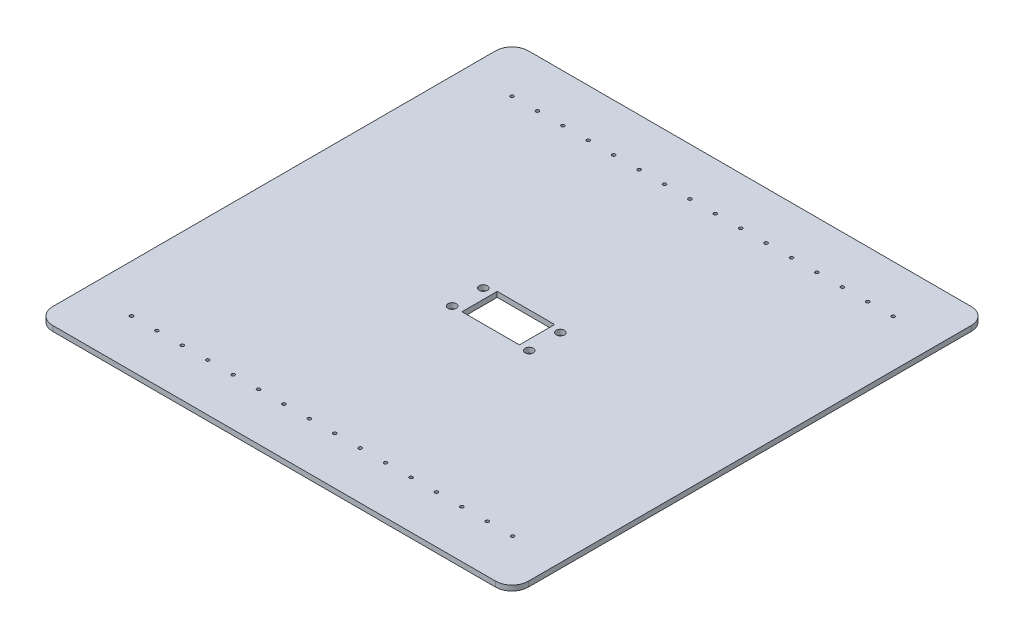
SolidWorks part; units mm, degrees
ref_plane "Front Plane" through (0, 0, 0) normal (0, 0, 1) x (1, 0, 0)
ref_plane "Top Plane" through (0, 0, 0) normal (0, 1, 0) x (1, 0, 0)
ref_plane "Right Plane" through (0, 0, 0) normal (1, 0, 0) x (0, 0, -1)
sketch "Sketch1" plane through (0, 0, 0) normal (0, 1, 0) x (1, 0, 0)
  line L0 (-145, 116) -> (145, 116) construction
  line L1 (145, -145) -> (-145, -145)
  line L2 (145, -145) -> (145, 145)
  line L3 (145, 145) -> (-145, 145)
  line L4 (-145, -145) -> (-145, 145)
  line L5 (145, -145) -> (-145, 145) construction
  line L6 (145, 145) -> (-145, -145) construction
  line L7 (-145, 87) -> (145, 87) construction
  line L8 (-145, 58) -> (145, 58) construction
  line L9 (-145, 29) -> (145, 29) construction
  line L10 (-145, 0) -> (145, 0) construction
  line L11 (-145, -29) -> (145, -29) construction
  line L12 (-145, -58) -> (145, -58) construction
  line L13 (-145, -87) -> (145, -87) construction
  line L14 (-145, -116) -> (145, -116) construction
  line L15 (-145, -145) -> (145, -145) construction
  point P0 (0, 0)
  dimension "D1" = 290
  dimension "D2" = 290
  dimension "D3" = 29
  dimension "D5" = 29
  dimension "D4" = 10
extrude "Base Plate" add sketch "Sketch1" along normal blind 3.175
hole_wizard "Caster Holes" positions "Sketch2" profile "Sketch3" hole size "Ø2.0" standard "ANSI Metric" end condition through all
sketch "Sketch2" plane through (0, 3.175, 0) normal (0, 1, 0) x (1, 0, 0)
  line L0 (-145, 116) -> (145, 116) construction
  line L2 (145, -145) -> (-145, 145) construction
  line L3 (-1.7463, 0) -> (1.7463, 0) construction
  line L4 (-145, -116) -> (145, -116) construction
  point P0 (-116, 116)
  point P8 (-100.506, 116)
  point P14 (-116, 116)
  point P24 (-85.012, 116)
  point P25 (-69.518, 116)
  point P26 (-54.024, 116)
  point P27 (-38.53, 116)
  point P28 (-23.036, 116)
  point P29 (-7.542, 116)
  point P30 (7.952, 116)
  point P31 (23.446, 116)
  point P32 (38.94, 116)
  point P33 (54.434, 116)
  point P34 (69.928, 116)
  point P35 (85.422, 116)
  point P36 (100.916, 116)
  point P37 (116.41, 116)
  point P40 (116.41, -116)
  point P41 (100.916, -116)
  point P42 (85.422, -116)
  point P43 (69.928, -116)
  point P44 (54.434, -116)
  point P45 (38.94, -116)
  point P46 (23.446, -116)
  point P47 (7.952, -116)
  point P48 (-7.542, -116)
  point P49 (-23.036, -116)
  point P50 (-38.53, -116)
  point P51 (-54.024, -116)
  point P52 (-69.518, -116)
  point P53 (-85.012, -116)
  point P54 (-100.506, -116)
  point P55 (-116, -116)
  dimension "D1" = 15.494
  dimension "D3" = 15.494
  dimension "D2" = 15
sketch "Sketch3" plane through (-116, 3.175, -116) normal (1, 0, 0) x (0, 0, 1)
  line L0 (0, 0) -> (0, 3.175)
  line L1 (0, 3.175) -> (1, 3.175)
  line L2 (1, 3.175) -> (1, 0)
  line L5 (1, 0) -> (0, 0)
  line L11 (0, -6.35) -> (0, 107.95) construction
  dimension "Thru Hole Dia." = 2
  dimension "Thru Hole Depth" = 3.175
fillet "Fillet1" radius 10 4 edges at (145, 1.5875, 145) (-145, 1.5875, 145) (145, 1.5875, -145) (-145, 1.5875, -145)
sketch "Sketch4" plane through (0, 0, 0) normal (0, -1, 0) x (1, 0, 0)
  line L0 (145, 0) -> (-145, 0) construction
  line L1 (-145, -135) -> (-145, 135) construction
  line L2 (0, -145) -> (0, 145) construction
  line L3 (-135, 145) -> (135, 145) construction
  point P6 (0, 0)
  point P12 (0, 0)
sketch "Sketch5" plane through (0, 3.175, 0) normal (0, 1, 0) x (1, 0, 0)
  line L0 (0, 145) -> (0, -145) construction
  line L1 (145, 0) -> (-145, 0) construction
  line L2 (0, 145) -> (0, -145) construction
  line L4 (-17.5, -13) -> (17.5, -13)
  line L5 (-17.5, -13) -> (-17.5, 8.5)
  line L6 (-17.5, 8.5) -> (17.5, 8.5)
  line L7 (17.5, -13) -> (17.5, 8.5)
  line L8 (-17.5, -13) -> (17.5, 8.5) construction
  line L9 (-17.5, 8.5) -> (17.5, -13) construction
  circle A0 centre (-23.5, 6) radius 2.5
  circle A2 centre (-23.5, -13) radius 2.5
  circle A3 centre (23.5, 6) radius 2.5
  circle A4 centre (23.5, -13) radius 2.5
  point P13 (0, -2.25)
  dimension "D1" = 5
  dimension "D2" = 23.5
  dimension "D3" = 6
  dimension "D4" = 19
  dimension "D5" = 6
  dimension "D6" = 6
extrude "Reflect Holes" cut sketch "Sketch5" against normal up to surface (3.175 mm away) up to face at (-100.506, 0, -115)
